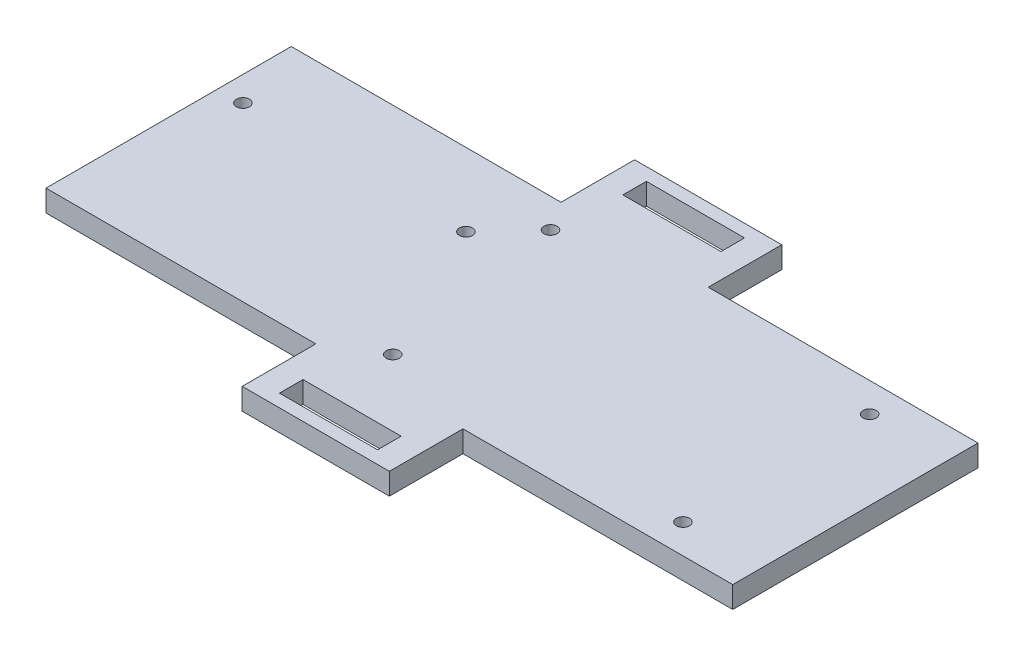
SolidWorks part; units mm, degrees
ref_plane "Front Plane" through (0, 0, 0) normal (0, 0, 1) x (1, 0, 0)
ref_plane "Top Plane" through (0, 0, 0) normal (0, 1, 0) x (1, 0, 0)
ref_plane "Right Plane" through (0, 0, 0) normal (1, 0, 0) x (0, 0, -1)
sketch "Sketch1" plane through (0, 0, 0) normal (0, 1, 0) x (1, 0, 0)
  line L0 (19.05, 31.75) -> (19.05, 50.8)
  line L1 (-88.9, -31.75) -> (-19.05, -31.75)
  line L2 (-88.9, -31.75) -> (-88.9, 31.75)
  line L3 (-88.9, 31.75) -> (-19.05, 31.75)
  line L4 (88.9, -31.75) -> (88.9, 31.75)
  line L5 (-88.9, -31.75) -> (88.9, 31.75) construction
  line L6 (-88.9, 31.75) -> (88.9, -31.75) construction
  line L7 (19.05, 50.8) -> (-19.05, 50.8)
  line L8 (-19.05, 50.8) -> (-19.05, 31.75)
  line L9 (19.05, 31.75) -> (88.9, 31.75)
  line L10 (-88.9, 0) -> (88.9, 0) construction
  line L11 (19.05, -31.75) -> (19.05, -50.8)
  line L12 (19.05, -50.8) -> (-19.05, -50.8)
  line L13 (-19.05, -50.8) -> (-19.05, -31.75)
  line L14 (19.05, -31.75) -> (88.9, -31.75)
  point P0 (0, 0)
  dimension "D1" = 177.8
  dimension "D2" = 63.5
  dimension "D3" = 19.05
  dimension "D4" = 38.1
extrude "Boss-Extrude1" add sketch "Sketch1" along normal blind 5.588
sketch "Sketch2" plane through (0, 5.588, 0) normal (0, 1, 0) x (1, 0, 0)
  line L0 (0, 0) -> (88.9, 0) construction
  line L1 (-12.7, 41.402) -> (12.7, 41.402)
  line L2 (-12.7, 41.402) -> (-12.7, 47.498)
  line L3 (-12.7, 47.498) -> (12.7, 47.498)
  line L4 (12.7, 41.402) -> (12.7, 47.498)
  line L5 (-12.7, 41.402) -> (12.7, 47.498) construction
  line L6 (-12.7, 47.498) -> (12.7, 41.402) construction
  line L7 (88.9, -31.75) -> (88.9, 31.75) construction
  line L8 (-12.7, -47.498) -> (12.7, -41.402) construction
  line L9 (-12.7, -41.402) -> (12.7, -47.498) construction
  line L10 (12.7, -41.402) -> (12.7, -47.498)
  line L11 (-12.7, -47.498) -> (12.7, -47.498)
  line L12 (-12.7, -41.402) -> (-12.7, -47.498)
  line L13 (-12.7, -41.402) -> (12.7, -41.402)
  point P0 (0, 44.45)
  point P5 (0, 0)
  point P15 (0, -44.45)
  dimension "D1" = 6.096
  dimension "D2" = 25.4
  dimension "D3" = 41.402
extrude "Cut-Extrude1" cut sketch "Sketch2" against normal through all
sketch "Sketch3" plane through (0, 5.588, 0) normal (0, 1, 0) x (1, 0, 0)
  point P0 (-14.1986, 24.1681)
  point P1 (68.4276, 24.1681)
  point P3 (68.4276, -24.1681)
  point P5 (-6.7056, -24.1681)
hole_wizard "M3 Clearance Hole1" positions "Sketch4" profile "Sketch5" hole size "M3" standard "ANSI Metric" end condition through all
sketch "Sketch4" plane through (0, 5.588, 0) normal (0, 1, 0) x (1, 0, 0)
  point P0 (-14.1986, 24.1681)
  point P3 (68.4276, 24.1681)
  point P6 (68.4276, -24.1681)
  point P9 (-6.7056, -24.1681)
sketch "Sketch5" plane through (-14.1986, 5.588, -24.1681) normal (1, 0, 0) x (0, 0, 1)
  line L0 (0, 0) -> (0, 5.588)
  line L1 (0, 5.588) -> (1.7, 5.588)
  line L2 (1.7, 5.588) -> (1.7, 0)
  line L5 (1.7, 0) -> (0, 0)
  line L11 (0, -6.35) -> (0, 107.95) construction
  dimension "Thru Hole Dia." = 3.4
  dimension "Thru Hole Depth" = 5.588
hole_wizard "M3 Clearance Hole2" positions "Sketch6" profile "Sketch7" hole size "M3" standard "ANSI Metric" end condition through all
sketch "Sketch6" plane through (0, 5.588, 0) normal (0, 1, 0) x (1, 0, 0)
  point P0 (-24.765, 12.827)
  point P3 (-82.4865, 12.827)
sketch "Sketch7" plane through (-24.765, 5.588, -12.827) normal (1, 0, 0) x (0, 0, 1)
  line L0 (0, 0) -> (0, 5.588)
  line L1 (0, 5.588) -> (1.7, 5.588)
  line L2 (1.7, 5.588) -> (1.7, 0)
  line L5 (1.7, 0) -> (0, 0)
  line L11 (0, -6.35) -> (0, 107.95) construction
  dimension "Thru Hole Dia." = 3.4
  dimension "Thru Hole Depth" = 5.588
